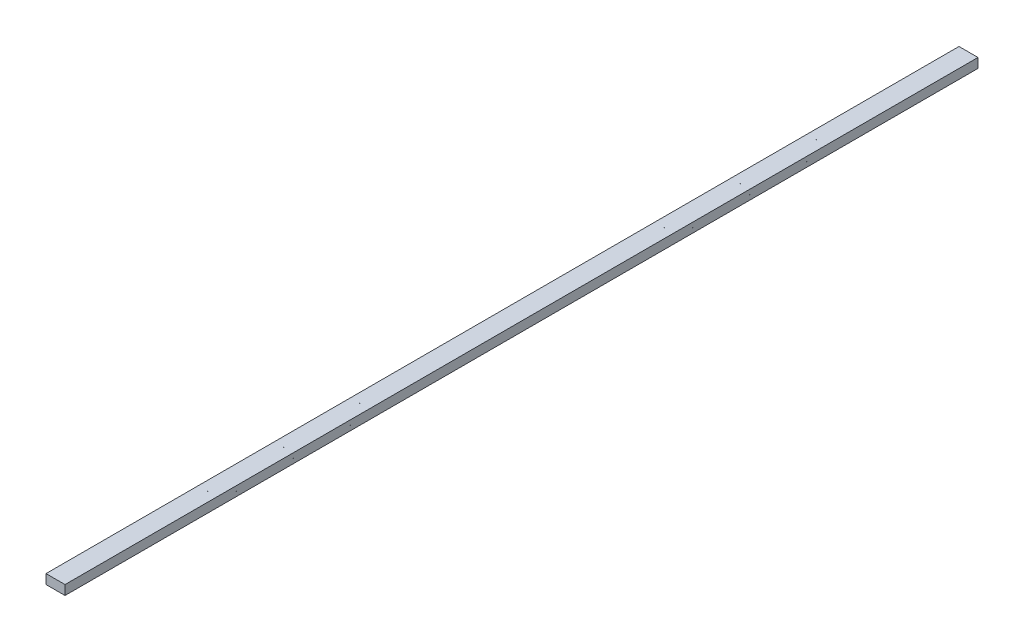
SolidWorks part; units mm, degrees
material "Pine"
ref_plane "Front Plane" through (0, 0, 0) normal (0, 0, 1) x (1, 0, 0)
ref_plane "Top Plane" through (0, 0, 0) normal (0, 1, 0) x (1, 0, 0)
ref_plane "Right Plane" through (0, 0, 0) normal (1, 0, 0) x (0, 0, -1)
sketch "Sketch1" plane through (0, 0, 0) normal (0, 0, 1) x (1, 0, 0)
  line L1 (0, 0) -> (101.6, 0)
  line L2 (0, 0) -> (0, 50.8)
  line L3 (0, 50.8) -> (101.6, 50.8)
  line L4 (101.6, 0) -> (101.6, 50.8)
  dimension "D1" = 101.6
  dimension "D2" = 50.8
extrude "Boss-Extrude1" add sketch "Sketch1" along normal blind 4876.8
sketch "Sketch2" plane through (0, 50.8, 0) normal (0, 1, 0) x (1, 0, 0)
  line L0 (50.8, 0) -> (50.8, -406.4) construction
  line L1 (101.6, 0) -> (0, 0) construction
  line L2 (0, 0) -> (0, -4876.8)
  circle A0 centre (50.8, -406.4) radius 0.8763
  dimension "D2" = 1.7526
  dimension "D1" = 406.4
extrude "Cut-Extrude1" cut sketch "Sketch2" against normal up to surface (50.8 mm away) contours A0 region at (50.8, 50.8, 406.4) up to face at (50.8, 0, 2438.4)
pattern_linear "LPattern1" count 11 spacing 406.4 along (0, 0, 1) of "Cut-Extrude1"
sketch "Sketch3" plane through (0, 50.8, 0) normal (0, 1, 0) x (1, 0, 0)
  line L0 (50.8, 0) -> (50.8, -50.8) construction
  line L1 (101.6, 0) -> (0, 0) construction
  line L2 (101.6, -2438.4) -> (0, -2438.4) construction
  line L3 (101.6, -4876.8) -> (101.6, 0) construction
  line L4 (0, -4876.8) -> (0, 0) construction
  circle A0 centre (50.8, -50.8) radius 0.8763
  circle A1 centre (50.8, -4724.4) radius 0.8763
  circle A2 centre (50.8, -101.6) radius 0.8763
  circle A3 centre (50.8, -152.4) radius 0.8763
  circle A4 centre (50.8, -4775.2) radius 0.8763
  circle A5 centre (50.8, -4826) radius 0.8763
  dimension "D2" = 1.7526
  dimension "D1" = 50.8
  dimension "D3" = 3
extrude "Cut-Extrude2" cut sketch "Sketch3" against normal up to surface (50.8 mm away) up to face at (50.8, 0, 4471.2763)
sketch "Sketch4" plane through (0, 0, 4876.8) normal (0, 0, 1) x (1, 0, 0)
  line L0 (0, 50.8) -> (101.6, 0) construction
  line L1 (101.6, 50.8) -> (0, 0) construction
  circle A0 centre (50.8, 25.4) radius 0.8763
  dimension "D1" = 1.7526
extrude "Cut-Extrude3" cut sketch "Sketch4" against normal up to surface (4876.8 mm away) up to face at (50.8, 25.4, 0)
sketch "Sketch6" plane through (0, 0, 0) normal (-1, 0, 0) x (0, 0, 1)
  line L0 (0, 25.4) -> (304.8, 25.4) construction
  line L1 (0, 50.8) -> (0, 0) construction
  circle A0 centre (304.8, 25.4) radius 0.8763
  circle A1 centre (609.6, 25.4) radius 0.8763
  circle A2 centre (914.4, 25.4) radius 0.8763
  circle A3 centre (1219.2, 25.4) radius 0.8763
  circle A4 centre (1524, 25.4) radius 0.8763
  circle A5 centre (1828.8, 25.4) radius 0.8763
  circle A6 centre (2133.6, 25.4) radius 0.8763
  circle A7 centre (2438.4, 25.4) radius 0.8763
  circle A8 centre (2743.2, 25.4) radius 0.8763
  circle A9 centre (3048, 25.4) radius 0.8763
  circle A10 centre (3352.8, 25.4) radius 0.8763
  circle A11 centre (3657.6, 25.4) radius 0.8763
  circle A12 centre (3962.4, 25.4) radius 0.8763
  circle A13 centre (4267.2, 25.4) radius 0.8763
  circle A14 centre (4572, 25.4) radius 0.8763
  dimension "D2" = 1.7526
  dimension "D1" = 304.8
  dimension "D3" = 15
extrude "Cut-Extrude4" cut sketch "Sketch6" against normal up to surface (101.6 mm away) up to face at (101.6, 25.4, 2438.4)
sketch "Sketch7" plane through (0, 0, 0) normal (-1, 0, 0) x (0, 0, 1)
  line L0 (0, 25.4) -> (50.8, 25.4) construction
  line L1 (0, 50.8) -> (0, 0) construction
  line L2 (2438.4, 0) -> (2438.4, 50.8) construction
  line L3 (4876.8, 0) -> (0, 0) construction
  line L4 (4876.8, 50.8) -> (0, 50.8) construction
  circle A0 centre (50.8, 25.4) radius 0.8763
  circle A1 centre (101.6, 25.4) radius 0.8763
  circle A2 centre (152.4, 25.4) radius 0.8763
  circle A3 centre (4724.4, 25.4) radius 0.8763
  circle A4 centre (4775.2, 25.4) radius 0.8763
  circle A5 centre (4826, 25.4) radius 0.8763
  dimension "D1" = 1.7526
  dimension "D2" = 50.8
  dimension "D3" = 3
extrude "Cut-Extrude5" cut sketch "Sketch7" against normal up to surface (101.6 mm away) up to face at (101.6, 25.4, 4572.8763)
equation "\"length\"= 1219.2 * 4"
equation "\"D1@Boss-Extrude1\"=\"length\""
equation "\"D1@LPattern1\"=\"length\" / 406.40 - 1"
equation "\"D3@Sketch6\"=\"length\" / 304.8 - 1"
